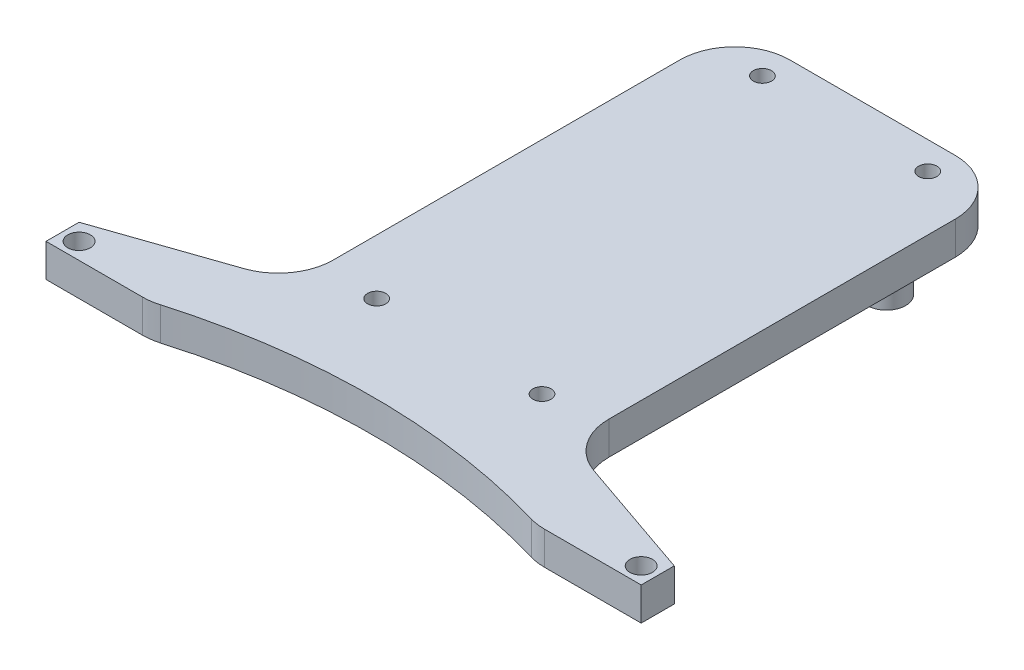
SolidWorks part; units mm, degrees
ref_plane "Front Plane" through (0, 0, 0) normal (0, 0, 1) x (1, 0, 0)
ref_plane "Top Plane" through (0, 0, 0) normal (0, 1, 0) x (1, 0, 0)
ref_plane "Right Plane" through (0, 0, 0) normal (1, 0, 0) x (0, 0, -1)
sketch "Sketch1" plane through (0, 0, 0) normal (0, 1, 0) x (1, 0, 0)
  line L0 (3, 3) -> (105, 3) construction
  line L1 (0, 0) -> (108, 0)
  line L2 (0, 0) -> (0, 6)
  line L4 (108, 0) -> (108, 6)
  line L5 (54, 16) -> (54, 0) construction
  line L6 (0, 6) -> (29, 16)
  line L7 (29, 16) -> (79, 16) construction
  line L8 (79, 16) -> (108, 6)
  line L9 (29, 16) -> (29, 96)
  line L10 (29, 96) -> (79, 96)
  line L11 (79, 96) -> (79, 16)
  line L12 (39, 21) -> (39, 91) construction
  line L13 (39, 91) -> (69, 91) construction
  line L14 (69, 91) -> (69, 21) construction
  line L15 (69, 21) -> (39, 21) construction
  line L16 (39, 21) -> (69, 91) construction
  circle A0 centre (3, 3) radius 2.05
  circle A1 centre (105, 3) radius 2.05
  circle A2 centre (39, 91) radius 1.65
  circle A3 centre (69, 91) radius 1.65
  circle A4 centre (39, 21) radius 1.65
  circle A5 centre (69, 21) radius 1.65
  point P10 (54, 0)
  point P11 (54, 3)
  point P17 (54, 16)
  point P26 (54, 91)
  point P27 (54, 96)
  point P28 (0, 0)
  dimension "D2" = 3
  dimension "D3" = 4.1
  dimension "D8" = 30
  dimension "D12" = 3.3
  dimension "D1" = 108
  dimension "D4" = 102
  dimension "D5" = 6
  dimension "D6" = 16
  dimension "D7" = 50
  dimension "D9" = 70
  dimension "D10" = 80
  dimension "D11" = 5
extrude "Boss-Extrude1" add sketch "Sketch1" along normal blind 6
sketch "Sketch2" plane through (0, 6, 0) normal (0, 1, 0) x (1, 0, 0)
  line L0 (19, 0) -> (89, 0)
  line L1 (0, 0) -> (108, 0) construction
  line L2 (79, 96) -> (29, 96) construction
  arc A0 (19, 0) -> (89, 0) centre (54, -114.7824) cw
  point P0 (54, 96)
  point P5 (54, 0)
  dimension "D2" = 120
  dimension "D1" = 70
extrude "Cut-Extrude1" cut sketch "Sketch2" against normal through all both and the other way through all
fillet "Fillet1" radius 10 6 edges at (79, 3, -96) (29, 3, -96) (89, 3, 0) (19, 3, 0) (79, 3, -16) (29, 3, -16)
sketch "Sketch3" plane through (0, 0, 0) normal (0, -1, 0) x (1, 0, 0)
  line L0 (36.5, -81) -> (71.5, -81) construction
  line L1 (69, -96) -> (39, -96) construction
  circle A0 centre (36.5, -81) radius 3.5
  circle A1 centre (71.5, -81) radius 3.5
  point P4 (54, -81)
  point P7 (54, -96)
  dimension "D1" = 7
  dimension "D2" = 35
  dimension "D3" = 15
extrude "Boss-Extrude2" add sketch "Sketch3" along normal blind 7.1
chamfer "Chamfer1" distance 2 angle 45 2 edges at (71.5, 0, -84.5) (36.5, 0, -84.5)
